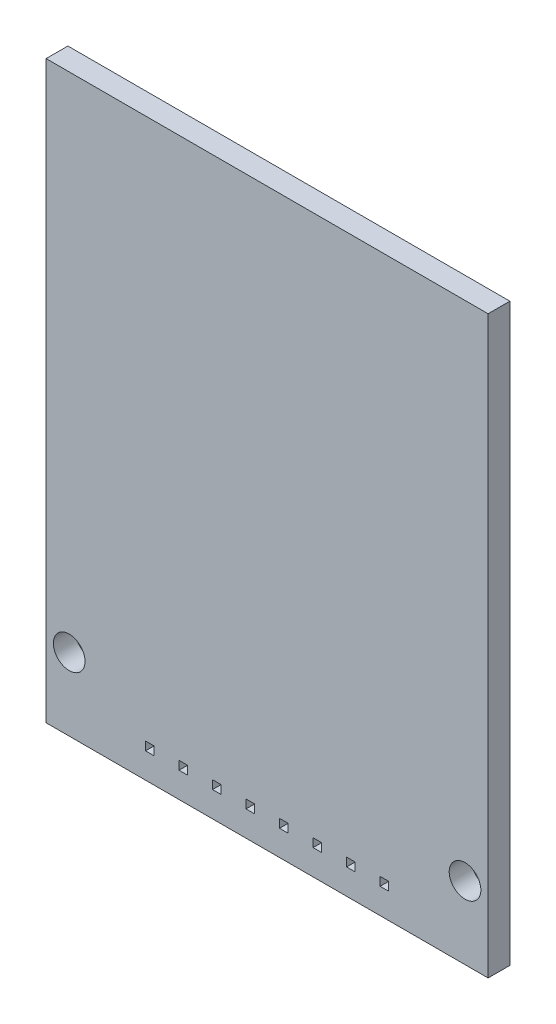
SolidWorks part; units mm, degrees
note: The reader was unsure of these and kept them because the rebuilt part matched: shared geometry of "Sketch2<2>".
ref_plane "Front Plane" through (0, 0, 0) normal (0, 0, 1) x (1, 0, 0)
ref_plane "Top Plane" through (0, 0, 0) normal (0, 1, 0) x (1, 0, 0)
ref_plane "Right Plane" through (0, 0, 0) normal (1, 0, 0) x (0, 0, -1)
sketch "Sketch1" plane through (0, 0, 0) normal (0, 0, 1) x (1, 0, 0)
  line L1 (16.75, -21.8) -> (-16.75, -21.8)
  line L2 (16.75, -21.8) -> (16.75, 21.8)
  line L3 (16.75, 21.8) -> (-16.75, 21.8)
  line L4 (-16.75, -21.8) -> (-16.75, 21.8)
  line L5 (16.75, -21.8) -> (-16.75, 21.8) construction
  line L6 (16.75, 21.8) -> (-16.75, -21.8) construction
  point P0 (0, 0)
  dimension "D1" = 33.5
  dimension "D2" = 43.6
extrude "Boss-Extrude1" add sketch "Sketch1" along normal blind 1.65
sketch "Sketch2" plane through (0, 0, 0) normal (0, 0, -1) x (-1, 0, 0)
  line L0 (0, 0) -> (0, -21.8) construction
  line L1 (16.75, -21.8) -> (-16.75, -21.8) construction
  line L3 (-1.595, -19.225) -> (-0.945, -19.225)
  line L4 (-1.595, -19.225) -> (-1.595, -19.875)
  line L5 (-1.595, -19.875) -> (-0.945, -19.875)
  line L6 (-0.945, -19.225) -> (-0.945, -19.875)
  line L7 (-1.595, -19.225) -> (-0.945, -19.875) construction
  line L8 (-1.595, -19.875) -> (-0.945, -19.225) construction
  point P5 (-1.27, -19.55)
  dimension "D1" = 0.65
  dimension "D2" = 2.25
  dimension "D3" = 2.54
extrude "Boss-Extrude2" add sketch "Sketch2" along normal blind 8.5 and the other way offset from surface (3.05 mm away) 1.4 other way up to face at (0, 0, 1.65)
extrude "Cut-Extrude1" cut sketch "Sketch2<2>" against normal through all both and the other way through all
sketch "Sketch2<2>" plane through (0, 0, 0) normal (0, 0, -1) x (-1, 0, 0) same geometry as "Sketch2"
pattern_linear "LPattern1" count 4 spacing 2.54 along (1, 0, 0) of "Cut-Extrude1"
mirror "Mirror1" about plane through (0, 0, 0) normal (1, 0, 0) of "Boss-Extrude2", "LPattern1"
sketch "Sketch3" plane through (0, 0, 0) normal (0, 0, 1) x (1, 0, 0)
  line L1 (0, 0) -> (0, -25.8877) construction
  line L2 (-16.75, -21.8) -> (16.75, -21.8) construction
  circle A0 centre (-15, -16.3) radius 1.2
  circle A1 centre (15, -16.3) radius 1.2
  dimension "D1" = 2.4
  dimension "D2" = 30
  dimension "D3" = 5.5
extrude "Cut-Extrude2" cut sketch "Sketch3" along normal through all
equation "\"screen width\"= 33.5mm"
equation "\"D1@Sketch1\"=\"screen width\""
